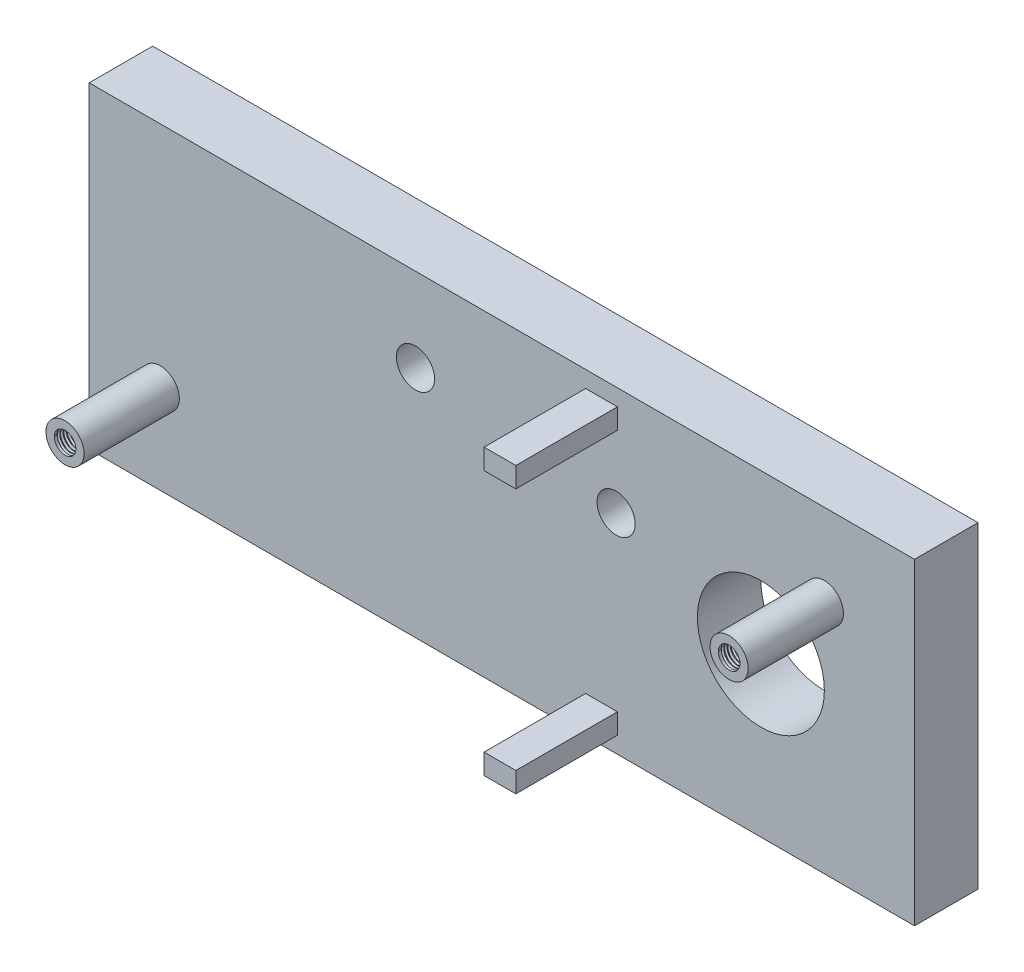
SolidWorks part; units mm, degrees
ref_plane "Front Plane" through (0, 0, 0) normal (0, 0, 1) x (1, 0, 0)
ref_plane "Top Plane" through (0, 0, 0) normal (0, 1, 0) x (1, 0, 0)
ref_plane "Right Plane" through (0, 0, 0) normal (1, 0, 0) x (0, 0, -1)
sketch "Sketch1" plane through (0, 0, 0) normal (0, 0, 1) x (1, 0, 0)
  line L0 (0, 0) -> (0, 32.877) construction
  line L1 (-32.5, 12.5) -> (32.5, 12.5)
  line L2 (-32.5, 12.5) -> (-32.5, -12.5)
  line L3 (-32.5, -12.5) -> (32.5, -12.5)
  line L4 (32.5, 12.5) -> (32.5, -12.5)
  line L5 (0, 0) -> (18.5499, 0) construction
  dimension "D1" = 65
  dimension "D2" = 25
  dimension "D3" = 32.5
  dimension "D4" = 12.5
extrude "Boss-Extrude1" add sketch "Sketch1" along normal mid plane 5 contours L1 L4 L3 L2
sketch "Sketch4" plane through (0, 0, 2.5) normal (0, 0, 1) x (1, 0, 0)
  line L0 (32.5, 12.5) -> (32.5, -12.5) construction
  line L1 (-32.5, -12.5) -> (32.5, -12.5) construction
  circle A0 centre (20.4, 0) radius 5
  dimension "D1" = 12.1
  dimension "D2" = 12.5
extrude "Cut-Extrude1" cut sketch "Sketch4" against normal blind 5
sketch "Sketch5" plane through (0, 0, 2.5) normal (0, 0, 1) x (1, 0, 0)
  line L0 (32.5, 12.5) -> (32.5, -12.5) construction
  line L2 (-32.5, 12.5) -> (32.5, 12.5) construction
  line L3 (-32.5, 12.5) -> (-32.5, -12.5) construction
  circle A0 centre (25.4, 6) radius 1.5021
  circle A1 centre (-26.9, -5.5) radius 1.5025
  point P8 (27.4366, 12.5)
  dimension "D1" = 7.1
  dimension "D2" = 6.5
  dimension "D3" = 5.6
  dimension "D4" = 18
extrude "Boss-Extrude2" add sketch "Sketch5" along normal blind 7.5
sketch "Sketch6" plane through (0, 0, 2.5) normal (0, 0, 1) x (1, 0, 0)
  line L0 (32.5, 12.5) -> (32.5, -12.5) construction
  line L1 (-32.5, 12.5) -> (32.5, 12.5) construction
  line L2 (-32.5, 12.5) -> (-32.5, -12.5) construction
  circle A0 centre (-6.8, 5.9) radius 1.5025
  circle A1 centre (9, 3.9) radius 1.5021
  dimension "D1" = 23.5
  dimension "D2" = 8.6
  dimension "D3" = 25.7
  dimension "D4" = 6.6
extrude "Cut-Extrude2" cut sketch "Sketch6" against normal blind 7.5
sketch "Sketch8" plane through (0, 0, 10) normal (0, 0, 1) x (1, 0, 0)
  circle A0 centre (-26.9, -5.5) radius 0.85
  circle A1 centre (25.4, 6) radius 0.85
extrude "Cut-Extrude3" cut sketch "Sketch8" against normal blind 5
thread "Thread1" pitch 0.25 method cut profile "Thread Profile1" start angle 0, offset 0, length 5, pitch 0.25, diameter 1.7
ref_plane "Plane1" through (-27.75, -5.5, 10) normal (0, -1, 0) x (-1, 0, 0)
sketch "Thread Profile1" plane through (-27.75, -5.5, 10) normal (0, -1, 0) x (-1, 0, 0)
  line L0 (0, 0) -> (0, 0.25) construction
  line L1 (0, 0) -> (0.1353, 0.0781)
  line L2 (0.1353, 0.0781) -> (0.1353, 0.1094)
  line L3 (0.1353, 0.1094) -> (0, 0.1875)
  line L4 (0.1353, 0.0937) -> (0, 0.0937) construction
  line L11 (0, 0) -> (0, 0.1875)
  point P2 (0, 0)
  dimension "Pitch" = 0.25
  dimension "Profile_Angle" = 60
  dimension "Profile_Land" = 0.0312
  dimension "Profile_Height" = 0.1353
thread "Thread2" pitch 0.25 method cut profile "Thread Profile2" start angle 0, offset 0, length 5, pitch 0.25, diameter 1.7
ref_plane "Plane2" through (24.55, 6, 10) normal (0, -1, 0) x (-1, 0, 0)
sketch "Thread Profile2" plane through (24.55, 6, 10) normal (0, -1, 0) x (-1, 0, 0)
  line L0 (0, 0) -> (0, 0.25) construction
  line L1 (0, 0) -> (0.1353, 0.0781)
  line L2 (0.1353, 0.0781) -> (0.1353, 0.1094)
  line L3 (0.1353, 0.1094) -> (0, 0.1875)
  line L4 (0.1353, 0.0937) -> (0, 0.0937) construction
  line L11 (0, 0) -> (0, 0.1875)
  point P2 (0, 0)
  dimension "Pitch" = 0.25
  dimension "Profile_Angle" = 60
  dimension "Profile_Land" = 0.0312
  dimension "Profile_Height" = 0.1353
sketch "Sketch14" plane through (0, 0, 2.5) normal (0, 0, 1) x (1, 0, 0)
  line L5 (6.6, 11.2) -> (9.1, 11.2)
  line L6 (6.6, 11.2) -> (6.6, 9.6)
  line L7 (6.6, 9.6) -> (9.1, 9.6)
  line L8 (9.1, 11.2) -> (9.1, 9.6)
  line L9 (-32.5, 12.5) -> (32.5, 12.5) construction
  line L10 (32.5, 12.5) -> (32.5, -12.5) construction
  line L11 (-32.5, -12.5) -> (32.5, -12.5) construction
  line L12 (6.6, -9.6) -> (9.1, -9.6)
  line L13 (6.6, -9.6) -> (6.6, -11.2)
  line L14 (6.6, -11.2) -> (9.1, -11.2)
  line L15 (9.1, -9.6) -> (9.1, -11.2)
  point P12 (7.85, -9.6)
  dimension "D1" = 2.5
  dimension "D2" = 1.6
  dimension "D3" = 25.9
  dimension "D4" = 2.9
  dimension "D5" = 2.5
  dimension "D6" = 1.6
  dimension "D7" = 2.9
  dimension "D8" = 25.9
extrude "Boss-Extrude3" add sketch "Sketch14" along normal blind 8
